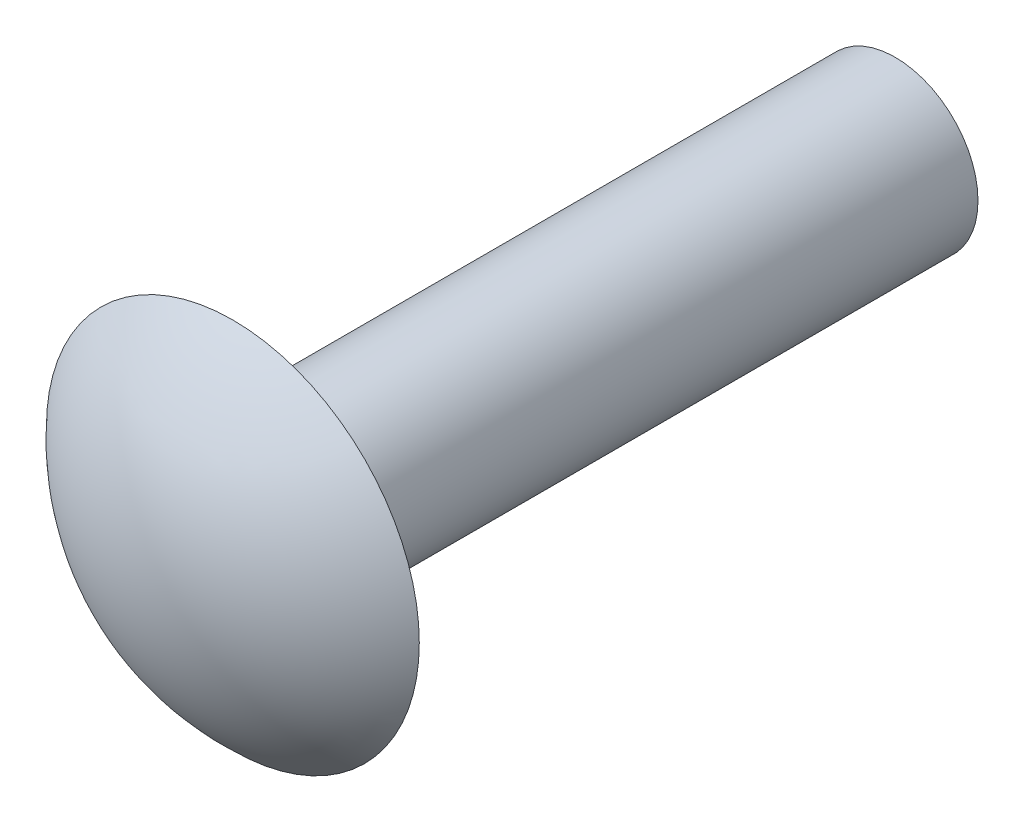
SolidWorks part; units mm, degrees
ref_plane "Front Plane" through (0, 0, 0) normal (0, 0, 1) x (1, 0, 0)
ref_plane "Top Plane" through (0, 0, 0) normal (0, 1, 0) x (1, 0, 0)
ref_plane "Right Plane" through (0, 0, 0) normal (1, 0, 0) x (0, 0, -1)
sketch "BaseBodySke" plane through (0, 0, 0) normal (0, 1, 0) x (1, 0, 0)
  line L0 (-7.1501, 3.175) -> (-3.175, 3.175)
  line L1 (0, 0) -> (0, 54.1082) construction
  line L2 (0, 0) -> (0, 28.575)
  line L3 (0, 28.575) -> (-3.175, 28.575)
  line L4 (-3.175, 3.175) -> (-3.175, 28.575)
  line L5 (-7.1501, 28.575) -> (-7.1501, 3.175) construction
  line L6 (-7.1501, 0) -> (-7.1501, 3.175) construction
  arc A0 (-7.1501, 3.175) -> (0, 0) centre (0, 9.6385) ccw
  dimension "Diameter" = 6.35
  dimension "Head_Diameter" = 14.3002
  dimension "Length" = 25.4
  dimension "Head_Depth" = 3.175
revolve "BaseBody" add sketch "BaseBodySke" angle 360 about L1
